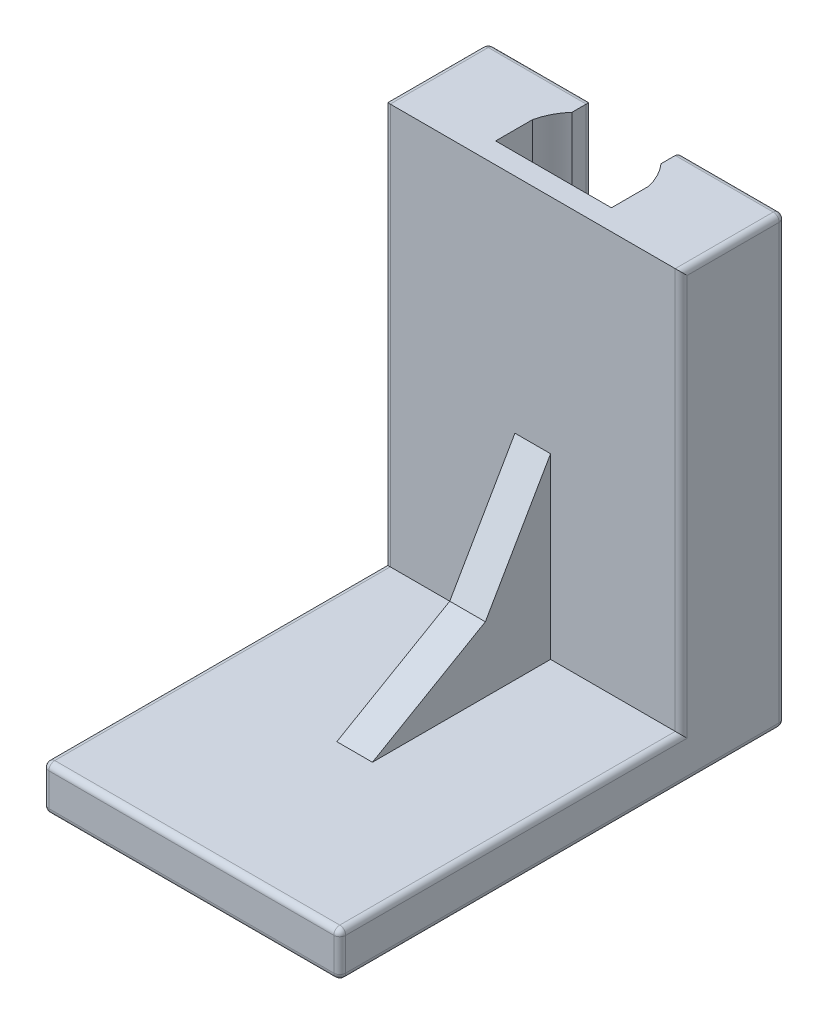
SolidWorks part; units mm, degrees
ref_plane "前视基准面" through (0, 0, 0) normal (0, 0, 1) x (1, 0, 0)
ref_plane "上视基准面" through (0, 0, 0) normal (0, 1, 0) x (1, 0, 0)
ref_plane "右视基准面" through (0, 0, 0) normal (1, 0, 0) x (0, 0, -1)
sketch "草图1" plane through (0, 0, 0) normal (1, 0, 0) x (0, 0, -1)
  line L1 (-7.5, 0) -> (7.5, 0)
  line L2 (-7.5, 0) -> (-7.5, 1.5)
  line L3 (-7.5, 1.5) -> (4, 1.5)
  line L6 (7.5, 0) -> (7.5, 15)
  line L7 (7.5, 15) -> (4, 15)
  line L8 (4, 1.5) -> (4, 15)
extrude "凸台-拉伸1" add sketch "草图1" along normal blind 5 and the other way blind 5
sketch "草图2" plane through (0, 0, 0) normal (1, 0, 0) x (0, 0, -1)
  line L0 (-2, 1.5) -> (1.8038, 3.6962)
  line L1 (4, 1.5) -> (-7.5, 1.5) construction
  line L2 (4, 7.5) -> (1.8038, 3.6962)
  line L3 (4, 15) -> (4, 1.5) construction
  line L4 (-2, 1.5) -> (4, 1.5)
  line L5 (4, 1.5) -> (4, 7.5)
extrude "凸台-拉伸2" add sketch "草图2" along normal blind 0.6 and the other way blind 0.6
sketch "草图3" plane through (0, 0, 0) normal (0, -1, 0) x (1, 0, 0)
  line L1 (-1.5, -1.5) -> (1.5, -1.5)
  line L2 (-1.5, -1.5) -> (-1.5, 1.5)
  line L3 (-1.5, 1.5) -> (1.5, 1.5)
  line L4 (1.5, -1.5) -> (1.5, 1.5)
extrude "凸台-拉伸3" add sketch "草图3" along normal blind 1
sketch "草图4" plane through (0, 0, 1.5) normal (0, 0, 1) x (1, 0, 0)
  line L0 (-1.95, -2.5) -> (1.95, -2.5)
  line L1 (-1.95, -2.5) -> (-1.95, -1.5556)
  line L2 (1.95, -2.5) -> (1.95, -1.5556)
  line L4 (-1.5, -1) -> (-1.5, 0) construction
  line L5 (-1.5, -0.6771) -> (1.5, -0.6771)
  arc A0 (-1.5, -0.6771) -> (-1.95, -1.5556) centre (0, -2) ccw
  arc A1 (1.95, -1.5556) -> (1.5, -0.6771) centre (0, -2) ccw
extrude "凸台-拉伸4" add sketch "草图4" along normal blind 1 and the other way blind 4
sketch "草图5" plane through (-1.95, 0, 0) normal (-1, 0, 0) x (0, 0, 1)
  line L0 (-1.95, -2.5) -> (-1.95, -1.5556)
  line L1 (-2.5, -2.5) -> (-1.95, -2.5)
  line L2 (-2.5, -2.5) -> (-2.5, -0.6771)
  line L3 (-2.5, -0.6771) -> (-1.5, -0.6771)
  line L4 (2.5, -2.5) -> (2.5, -0.6771)
  line L5 (1.95, -2.5) -> (1.95, -1.5556)
  line L7 (1.5, -0.6771) -> (2.5, -0.6771)
  line L8 (1.95, -2.5) -> (2.5, -2.5)
  arc A0 (-1.5, -0.6771) -> (-1.95, -1.5556) centre (0, -2) ccw
  arc A3 (1.95, -1.5556) -> (1.5, -0.6771) centre (0, -2) ccw
extrude "切除-拉伸1" cut sketch "草图5" against normal up to next
sketch "草图6" plane through (0, 15, 0) normal (0, 1, 0) x (-1, 0, 0)
  line L0 (5, -7.5) -> (-5, -7.5) construction
  line L1 (1.5, -7.5) -> (-1.5, -7.5)
  line L2 (1.5, -7.5) -> (1.5, -6.8229)
  line L4 (-1.5, -7.5) -> (-1.5, -6.8229)
  line L5 (1.95, -4.7) -> (-1.95, -4.7)
  line L6 (1.95, -4.7) -> (1.95, -5.9444)
  line L7 (-1.95, -4.7) -> (-1.95, -5.9444)
  arc A0 (1.5, -6.8229) -> (1.95, -5.9444) centre (0, -5.5) ccw
  arc A1 (-1.95, -5.9444) -> (-1.5, -6.8229) centre (0, -5.5) ccw
extrude "切除-拉伸2" cut sketch "草图6" against normal blind 9.45
fillet "圆角1" radius 0.1 4 edges at (1.95, -2.5, 0) (0, -2.5, -1.95) (-1.95, -2.5, 0) (0, -2.5, 1.95)
fillet "圆角2" radius 0.2 20 edges at (-3.25, 15, -7.5) (0, 0, -7.5) (3.25, 15, -7.5) (1.5, 10.275, -7.5) (0, 5.55, -7.5) (-1.5, 10.275, -7.5) (-5, 0, 0) (-5, 7.5, -7.5) (-5, 15, -5.75) (-5, 8.25, -4) (-5, 1.5, 1.75) (-5, 0.75, 7.5) (5, 1.5, 1.75) (5, 8.25, -4) (5, 15, -5.75) (5, 7.5, -7.5) (5, 0, 0) (5, 0.75, 7.5) (0, 1.5, 7.5) (0, 0, 7.5)
